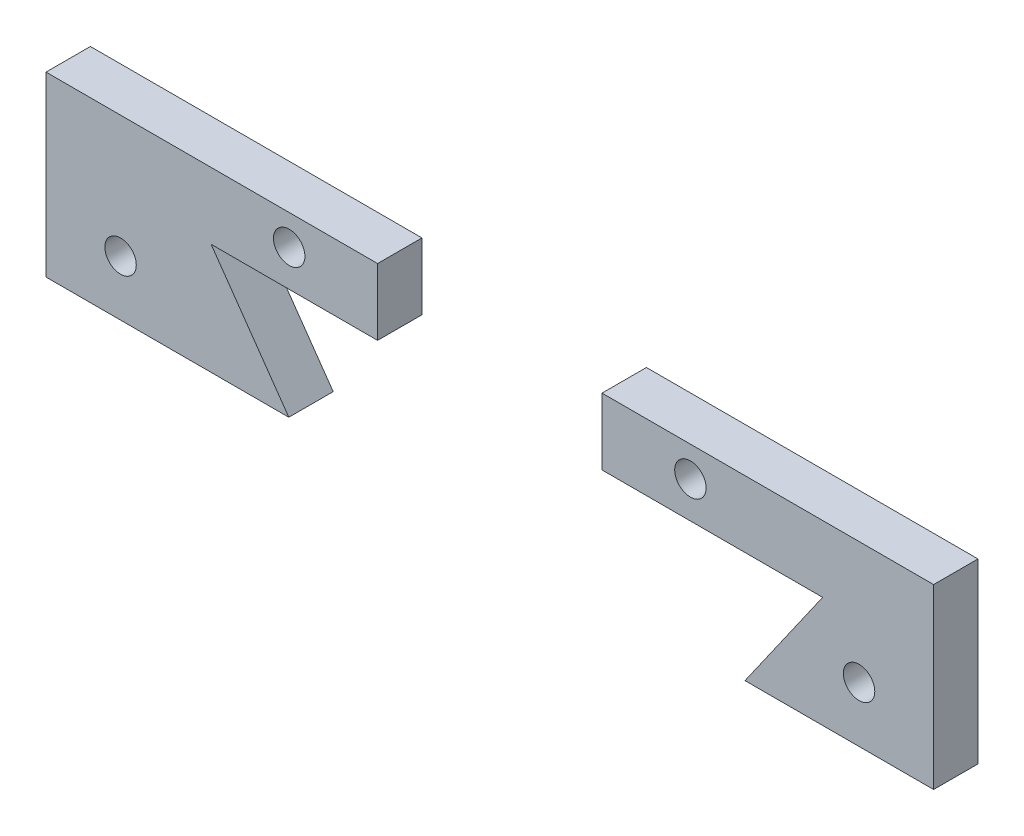
SolidWorks part; units mm, degrees
material "SAE F5 Wool Felt"
ref_plane "Front Plane" through (0, 0, 0) normal (0, 0, 1) x (1, 0, 0)
ref_plane "Top Plane" through (0, 0, 0) normal (0, 1, 0) x (1, 0, 0)
ref_plane "Right Plane" through (0, 0, 0) normal (1, 0, 0) x (0, 0, -1)
sketch "Sketch4" plane through (0, 0, 0) normal (0, 0, 1) x (1, 0, 0)
  point P0 (0, 0)
  line B0 (-63.5, -15.875) -> (63.5, -15.875)
  line B1 (63.5, 0) -> (36.5092, 0)
  line B2 (36.5092, 0) -> (47.625, 15.875)
  line B3 (47.625, 15.875) -> (16.0563, 15.875)
  line B4 (-39.8731, 15.875) -> (-28.7573, 0)
  line B5 (-28.7573, 0) -> (-63.5, 0)
  line B6 (-36.5092, 0) -> (-47.625, 15.875)
  line B7 (-47.625, 15.875) -> (-39.8731, 15.875)
  line B8 (-16.0563, 15.875) -> (-16.0563, -3.175)
  line B9 (-16.0563, 15.875) -> (-39.8731, 15.875)
  line B10 (-63.5, 0) -> (-63.5, 31.75)
  line B11 (-63.5, 31.75) -> (63.5, 31.75)
  line B12 (-16.0563, 15.875) -> (16.0563, 15.875)
  line B13 (0, 31.75) -> (0, -15.875) construction
  line B14 (-36.5092, 0) -> (36.5092, 0) construction
  line B15 (-28.702, 21.082) -> (28.702, 21.082) construction
  line B16 (-25.4, -8.001) -> (25.4, -8.001) construction
  line B17 (-52.832, 7.9375) -> (52.832, 7.9375) construction
  circle B18 centre (0, 6.35) radius 18.669 construction
sketch_block_instance "dovetail pair-1"
sketch_block "dovetail pair" parameters "D8"=37.338, "D1"=55, "D2"=127, "D3"=6.35, "D4"=15.875, "D5"=31.75, "D6"=95.25, "D7"=19.05, "D9"=55, "D10"=31.75, "D11"=50.8, "D12"=23.876, "D13"=7.874, "D14"=10.668, "D15"=34.798, "D16"=21.082, "D17"=7.9375
sketch "Sketch1" plane through (0, 0, 0) normal (0, 0, 1) x (1, 0, 0)
  line L0 (-28.7573, 0) -> (-63.5, 0) construction
  line L1 (-39.8731, 15.875) -> (-28.7573, 0) construction
  line L2 (36.5092, 0) -> (47.625, 15.875) construction
  line L3 (63.5, 0) -> (36.5092, 0) construction
  line L4 (-16.0563, 15.875) -> (-39.8731, 15.875) construction
  line L5 (47.625, 15.875) -> (16.0563, 15.875) construction
  line L6 (-28.7573, 0) -> (-63.5, 0)
  line L7 (-39.8731, 15.875) -> (-28.7573, 0)
  line L8 (36.5092, 0) -> (47.625, 15.875)
  line L9 (63.5, 0) -> (36.5092, 0)
  line L10 (-16.0563, 15.875) -> (-39.8731, 15.875)
  line L11 (47.625, 15.875) -> (16.0563, 15.875)
  line L12 (-63.5, 0) -> (-63.5, 25.4)
  line L13 (-63.5, 25.4) -> (-16.0563, 25.4)
  line L14 (-16.0563, 25.4) -> (-16.0563, 15.875)
  line L15 (16.0563, 15.875) -> (16.0563, 25.4)
  line L16 (16.0563, 25.4) -> (63.5, 25.4)
  line L17 (63.5, 25.4) -> (63.5, 0)
  dimension "D1" = 25.4
extrude "Boss-Extrude1" add sketch "Sketch1" along normal blind 6.35
hole_wizard "#8 Clearance Hole1" positions "Sketch2" profile "Sketch3" hole size "#8" standard "ANSI Inch" end condition through all
sketch "Sketch2" plane through (0, -15.875, 6.35) normal (0, 0, 1) x (1, 0, 0)
  point P32 (-52.832, 23.8125)
  point P34 (-28.702, 36.957)
  point P36 (28.702, 36.957)
  point P38 (52.832, 23.8125)
sketch "Sketch3" plane through (-52.832, 7.9375, 6.35) normal (1, 0, 0) x (0, -1, 0)
  line L0 (0, 0) -> (0, 6.35)
  line L1 (0, 6.35) -> (2.2479, 6.35)
  line L2 (2.2479, 6.35) -> (2.2479, 0)
  line L3 (2.2479, 0) -> (0, 0)
  line L4 (0, -6.35) -> (0, 107.95) construction
  dimension "Thru Hole Dia." = 4.4958
  dimension "Thru Hole Depth" = 6.35
equation "\"dovetail-angle\" = 55"
equation "\"dovetail-stock-width\" = 5"
equation "\"dovetail-stock-height\" = 1.25"
equation "\"dovetail-depth\" = 0.5 * \"dovetail-stock-height\""
equation "\"dovetail-throat-width\" = \"dovetail-stock-width\" - (2 * \"dovetail-depth\")"
equation "\"delta-x\" = 6"
equation "\"delta-y\" = 3"
equation "\"gib-thickness\" = 0.25"
equation "\"x-slide-length\" = \"dovetail-stock-width\" + \"delta-x\""
equation "\"y-slide-length\" = \"dovetail-stock-width\" + \"delta-y\""
equation "\"dog-point-diam\" = .149"
equation "\"dog-point-length\" = .067"
equation "\"dovetail-double-height\" = 2 * \"dovetail-depth\" + 0.5"
equation "\"acme-major-diam\" = .5"
equation "\"acme-pitch-diam\" = 0.45"
equation "\"acme-minor-diam\" = 0.4"
equation "\"acme-nut-od\" = 1.47"
equation "\"acme-nut-length\" = 1"
equation "\"acme-nut-trim-height\" = .75"
equation "\"screw-bearing-od\" = 0.5"
equation "\"screw-bearing-length\" = .375"
equation "\"screw-bearing-id\" = .375"
equation "\"end-plate-thickness\" = \"screw-bearing-length\""
equation "\"screw-add-length\" = 2 * \"end-plate-thickness\" + 1 + 0.5"
equation "\"x-screw-length\" = \"x-slide-length\" + \"screw-add-length\""
equation "\"y-screw-length\" = \"y-slide-length\" + \"screw-add-length\""
equation "\"acme-nut-mount-hole-space-horz\" = 0.95"
equation "\"acme-nut-mount-hole-space-vert\" = 0.5 * \"acme-nut-length\""
equation "\"vise-hole-center-dist\" = 6.75"
equation "\"wiper_plate_clearance\" = .03"
equation "\"D2@dovetail pair\"=\"dovetail-stock-width\""
equation "\"D1@dovetail pair\"=\"dovetail-angle\""
equation "\"D3@dovetail pair\"=\"gib-thickness\""
equation "\"D4@dovetail pair\"=\"dovetail-depth\""
equation "\"D5@dovetail pair\"=\"dovetail-stock-height\""
equation "\"D6@dovetail pair\"=\"dovetail-throat-width\""
equation "\"D10@dovetail pair\"=\"dovetail-stock-height\""
equation "\"D7@dovetail pair\"=\"acme-nut-trim-height\""
equation "\"D8@dovetail pair\"=\"acme-nut-od\""
equation "\"D9@dovetail pair\"=\"dovetail-angle\""
equation "\"D17@dovetail pair\"=\"dovetail-depth\"/2"
